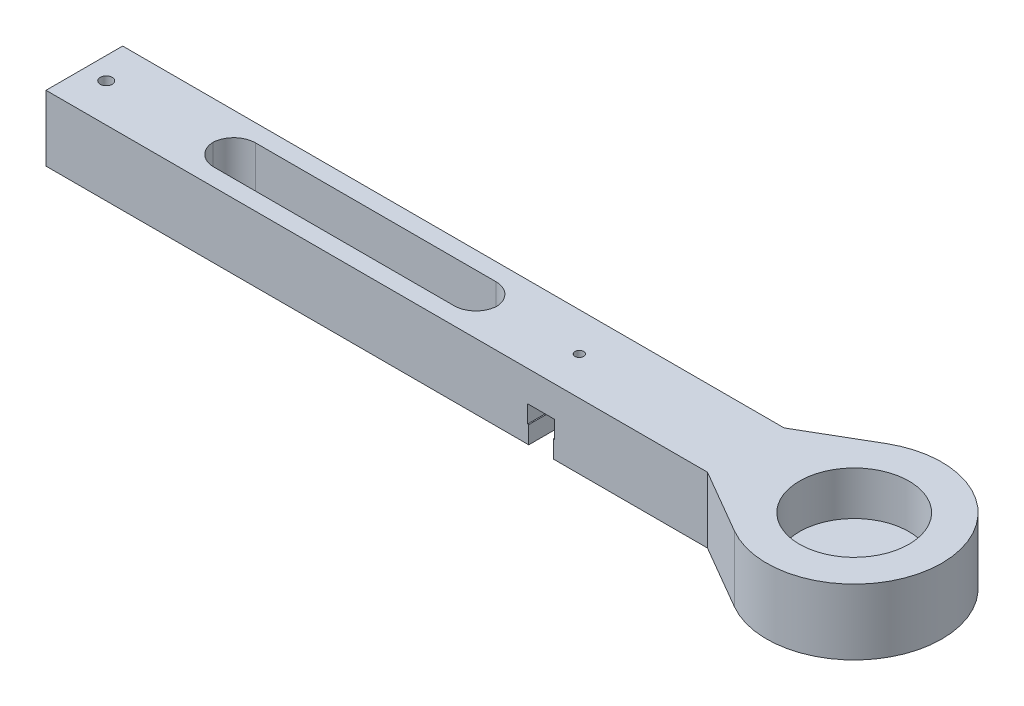
SolidWorks part; units mm, degrees
material "PLA "
ref_plane "Front Plane" through (0, 0, 0) normal (0, 0, 1) x (1, 0, 0)
ref_plane "Top Plane" through (0, 0, 0) normal (0, 1, 0) x (1, 0, 0)
ref_plane "Right Plane" through (0, 0, 0) normal (1, 0, 0) x (0, 0, -1)
sketch "Sketch1" plane through (0, 0, 0) normal (0, 1, 0) x (1, 0, 0)
  line L0 (0, 0) -> (-247, 0) construction
  line L1 (-247, 0) -> (-447, 0) construction
  dimension "D1" = 247
  dimension "D2" = 200
sketch "Sketch2" plane through (0, 0, 0) normal (0, 1, 0) x (1, 0, 0)
  line L1 (-247, -17.5) -> (0, -17.5)
  line L2 (-247, -17.5) -> (-247, 17.5)
  line L3 (-247, 17.5) -> (0, 17.5)
  line L4 (0, -17.5) -> (0, 17.5)
  point P4 (-247, 0)
  dimension "D1" = 35
extrude "Boss-Extrude1" add sketch "Sketch2" along normal blind 30 contours L1 L4 L3 L2
sketch "Sketch3" plane through (0, 0, 0) normal (0, -1, 0) x (1, 0, 0)
  line L0 (0, 0) -> (-21, 0) construction
  line L1 (0, 0) -> (-247, 0) construction
  circle A0 centre (-21, 0) radius 5.6
  dimension "D2" = 11.2
  dimension "D1" = 21
extrude "Cut-Extrude1" cut sketch "Sketch3" against normal through all
sketch "Sketch4" plane through (0, 30, 0) normal (0, 1, 0) x (1, 0, 0)
  line L0 (0, -17.5) -> (0, 17.5) construction
  line L1 (-14.9, 3.5218) -> (-21, 7.0437)
  line L2 (-21, 7.0437) -> (-27.1, 3.5218)
  line L3 (-27.1, 3.5218) -> (-27.1, -3.5218)
  line L4 (-27.1, -3.5218) -> (-21, -7.0437)
  line L5 (-21, -7.0437) -> (-14.9, -3.5218)
  line L6 (-14.9, -3.5218) -> (-14.9, 3.5218)
  line L7 (-27.1, 0) -> (-14.9, 0)
  circle A0 centre (-21, 0) radius 6.1 construction
  dimension "D1" = 12.2
extrude "Cut-Extrude2" cut sketch "Sketch4" against normal blind 22 contours L1 L2 L3 L4 L5 L6
sketch "Sketch5" plane through (0, 0, 0) normal (1, 0, 0) x (0, 0, -1)
  line L0 (0, 8) -> (0, 1) construction
  line L1 (-3.5218, 8) -> (3.5218, 8) construction
  line L2 (0, 1) -> (0, -2.0977) construction
  line L3 (2.5, 1) -> (2.5, -2.0977)
  line L4 (-2.5, 1) -> (-2.5, -2.0977)
  arc A0 (2.5, 1) -> (-2.5, 1) centre (0, 1) ccw
  arc A1 (-2.5, -2.0977) -> (2.5, -2.0977) centre (0, -2.0977) ccw
  point P5 (0, -0.5488)
  dimension "D1" = 7
  dimension "D2" = 5
sketch "Sketch6" plane through (0, 0, 0) normal (1, 0, 0) x (0, 0, -1)
  line L0 (0, 8) -> (0, 16) construction
  line L1 (-3.5218, 8) -> (3.5218, 8) construction
  line L2 (-17.5, 30) -> (17.5, 30) construction
  line L3 (-11.0435, 16) -> (11.453, 16)
  line L4 (-11.0435, 16) -> (-11.0435, 30)
  line L5 (-11.0435, 30) -> (11.453, 30)
  line L6 (11.453, 16) -> (11.453, 30)
  dimension "D1" = 8
extrude "Boss-Extrude3" add sketch "Sketch6" against normal blind 38
sketch "Sketch7" plane through (0, 0, 17.5) normal (0, 0, 1) x (1, 0, 0)
  line L0 (-21, 16) -> (-14.9, 16) construction
  line L1 (-27.1, 16) -> (-21, 16) construction
  line L2 (-27.1, 8) -> (-27.1, 16) construction
  line L3 (-14.9, 8) -> (-14.9, 16) construction
  line L4 (-15.4, 0) -> (-15.4, 8) construction
  line L5 (-26.6, 8) -> (-26.6, 0) construction
  line L6 (-21, 16) -> (-14.9, 16)
  line L7 (-27.1, 16) -> (-21, 16)
  line L8 (-27.1, 8) -> (-27.1, 16)
  line L9 (-14.9, 8) -> (-14.9, 16)
  line L10 (-15.4, 0) -> (-15.4, 8)
  line L11 (-26.6, 8) -> (-26.6, 0)
  line L12 (-27.1, 8) -> (-26.6, 8)
  line L13 (-15.4, 8) -> (-14.9, 8)
  line L14 (-26.6, 0) -> (-15.4, 0)
extrude "Cut-Extrude4" cut sketch "Sketch7" against normal up to vertex (17.5 mm away) up to point (-14.9, 30, 0)
sketch "Sketch9" plane through (0, 30, 0) normal (0, 1, 0) x (1, 0, 0)
  line L0 (-27.1, 3.5218) -> (-14.9, -3.5218) construction
  line L1 (-27.1, -3.5218) -> (-14.9, 3.5218) construction
  line L6 (-14.9, 3.5218) -> (-21, 7.0437)
  line L7 (-21, 7.0437) -> (-27.1, 3.5218)
  line L8 (-27.1, 3.5218) -> (-27.1, -3.5218)
  line L9 (-27.1, -3.5218) -> (-21, -7.0437)
  line L10 (-21, -7.0437) -> (-14.9, -3.5218)
  line L11 (-14.9, -3.5218) -> (-14.9, 3.5218)
  line L12 (-14.9, 3.5218) -> (-21, 7.0437) construction
  line L13 (-21, 7.0437) -> (-27.1, 3.5218) construction
  line L14 (-27.1, 3.5218) -> (-27.1, -3.5218) construction
  line L15 (-27.1, -3.5218) -> (-21, -7.0437) construction
  line L16 (-21, -7.0437) -> (-14.9, -3.5218) construction
  line L17 (-14.9, -3.5218) -> (-14.9, 3.5218) construction
  circle A0 centre (-21, 0) radius 2
  dimension "D2" = 4
  dimension "D1" = 0
extrude "Cut-Extrude5" cut sketch "Sketch9" against normal blind 38
sketch "Sketch15" plane through (0, 30, 0) normal (0, 1, 0) x (1, 0, 0)
  line L0 (-247, 0) -> (-237, 0) construction
  line L1 (0, 0) -> (-247, 0) construction
  circle A0 centre (-237, 0) radius 2.75
  dimension "D2" = 5.5
  dimension "D1" = 10
extrude "Cut-Extrude10" cut sketch "Sketch15" against normal blind 9
sketch "Sketch16" plane through (0, 0, 0) normal (0, -1, 0) x (1, 0, 0)
  line L1 (-241.1302, 2.6504) -> (-241.3604, -2.2517)
  line L2 (-241.3604, -2.2517) -> (-237.2302, -4.9021)
  line L3 (-237.2302, -4.9021) -> (-232.8698, -2.6504)
  line L4 (-232.8698, -2.6504) -> (-232.6396, 2.2517)
  line L5 (-232.6396, 2.2517) -> (-236.7698, 4.9021)
  line L6 (-236.7698, 4.9021) -> (-241.1302, 2.6504)
  circle A0 centre (-237, 0) radius 2.75 construction
  circle A1 centre (-237, 0) radius 2.75 construction
  circle A2 centre (-237, 0) radius 4.25 construction
  dimension "D1" = 8.5
extrude "Cut-Extrude11" cut sketch "Sketch16" against normal up to surface (21 mm away) up to face at (-237, 21, 2.75)
sketch "Sketch17" plane through (0, 30, 0) normal (0, 1, 0) x (1, 0, 0)
  line L0 (0, 0) -> (-247, 0) construction
  line L2 (-58.6673, -9.5384) -> (-188.3327, -9.5384)
  line L3 (-58.6673, -9.5384) -> (-58.6673, 9.5384)
  line L4 (-58.6673, 9.5384) -> (-188.3327, 9.5384)
  line L5 (-188.3327, -9.5384) -> (-188.3327, 9.5384)
  line L6 (-58.6673, -9.5384) -> (-188.3327, 9.5384) construction
  line L7 (-58.6673, 9.5384) -> (-188.3327, -9.5384) construction
  point P4 (-123.5, 0)
extrude "Cut-Extrude12" cut sketch "Sketch17" against normal through all
fillet "Fillet1" radius 10 4 edges at (-58.6673, 15, 9.5384) (-58.6673, 15, -9.5384) (-188.3327, 15, -9.5384) (-188.3327, 15, 9.5384)
sketch "Sketch19" plane through (0, 0, 0) normal (1, 0, 0) x (0, 0, -1)
  line L5 (17.5, 0) -> (17.5, 30)
  line L6 (17.5, 30) -> (-17.5, 30)
  line L7 (-17.5, 30) -> (-17.5, 0)
  line L8 (-17.5, 0) -> (17.5, 0)
  line L9 (17.5, 0) -> (17.5, 30)
  line L10 (17.5, 30) -> (-17.5, 30)
  line L11 (-17.5, 30) -> (-17.5, 0)
  line L12 (-17.5, 0) -> (17.5, 0)
  dimension "D1" = 0
extrude "Boss-Extrude5" add sketch "Sketch19" along normal blind 55
sketch "Sketch18" plane through (0, 30, 0) normal (0, 1, 0) x (1, 0, 0)
  line L0 (84.4055, -34.5857) -> (84.4055, 34.5857) construction
  line L1 (55, 17.5) -> (55, -17.5)
  line L2 (55, -17.5) -> (84.4055, -34.5857)
  line L5 (84.4055, 34.5857) -> (55, 17.5)
  line L6 (55, 0) -> (84.4055, 0) construction
  arc A1 (84.4055, -34.5857) -> (84.4055, 34.5857) centre (104.5011, 0) ccw
  point P5 (87.6598, -33.7819)
  point P7 (144.5011, 0)
  dimension "D1" = 40
extrude "Boss-Extrude4" add sketch "Sketch18" against normal up to vertex (30 mm away) up to point (55, 0, 17.5)
sketch "Sketch20" plane through (0, 0, 0) normal (0, -1, 0) x (1, 0, 0)
  circle A0 centre (104.5011, 0) radius 25
  dimension "D1" = 50
sketch "Sketch21" plane through (0, 30, 0) normal (0, 1, 0) x (1, 0, 0)
  circle A1 centre (104.5011, 0) radius 25
  circle A2 centre (104.5011, 0) radius 25
  dimension "D1" = 0
extrude "Cut-Extrude14" cut sketch "Sketch21" against normal blind 20
equation "\"2.5c\"=10"
